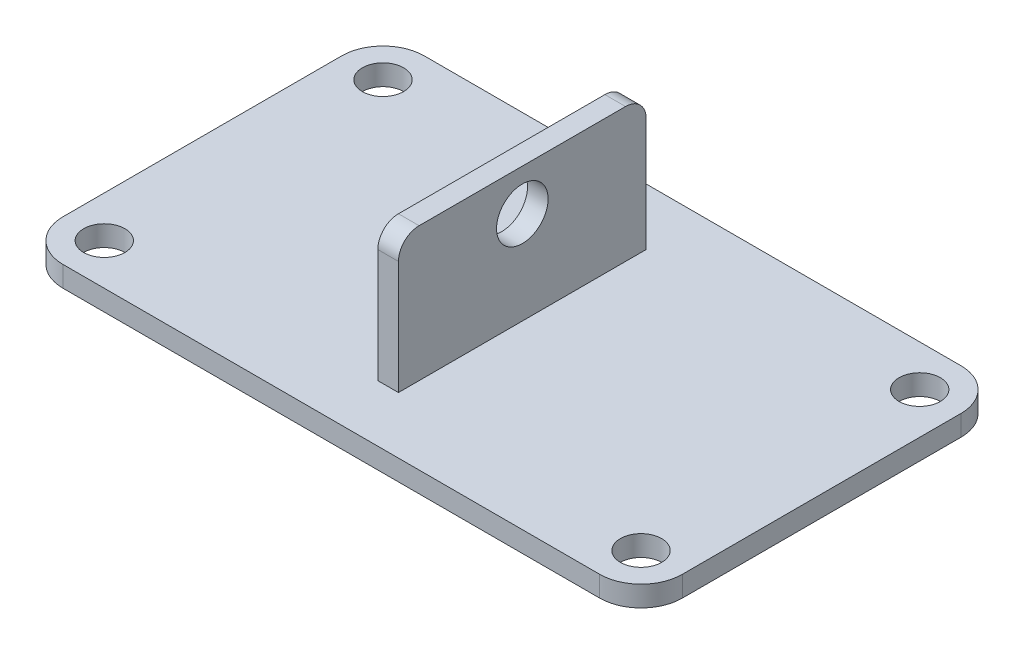
SolidWorks part; units mm, degrees
ref_plane "Front Plane" through (0, 0, 0) normal (0, 0, 1) x (1, 0, 0)
ref_plane "Top Plane" through (0, 0, 0) normal (0, 1, 0) x (1, 0, 0)
ref_plane "Right Plane" through (0, 0, 0) normal (1, 0, 0) x (0, 0, -1)
sketch "Sketch1" plane through (0, 0, 0) normal (0, 1, 0) x (1, 0, 0)
  line L1 (-130, -87.5) -> (130, -87.5)
  line L2 (-150, -67.5) -> (-150, 67.5)
  line L3 (-130, 87.5) -> (130, 87.5)
  line L4 (150, -67.5) -> (150, 67.5)
  line L5 (-150, -87.5) -> (150, 87.5) construction
  line L6 (-150, 87.5) -> (150, -87.5) construction
  line L7 (-5, -60) -> (5, -60)
  line L8 (-5, -60) -> (-5, 60)
  line L9 (-5, 60) -> (5, 60)
  line L10 (5, -60) -> (5, 60)
  line L11 (-5, -60) -> (5, 60)
  line L12 (-5, 60) -> (5, -60) construction
  arc A0 (-150, -67.5) -> (-130, -87.5) centre (-130, -67.5) ccw
  arc A1 (130, -87.5) -> (150, -67.5) centre (130, -67.5) ccw
  arc A2 (150, 67.5) -> (130, 87.5) centre (130, 67.5) ccw
  arc A3 (-150, 67.5) -> (-130, 87.5) centre (-130, 67.5) cw
  circle A4 centre (130, 67.5) radius 10
  circle A5 centre (130, -67.5) radius 10
  circle A6 centre (-130, 67.5) radius 10
  circle A7 centre (-130, -67.5) radius 10
  point P0 (0, 0)
  point P6 (0, 0)
  point P27 (0, 0)
  point P28 (0, 0)
  dimension "D3" = 20
  dimension "D4" = 10
  dimension "D6" = 20
  dimension "D1" = 175
  dimension "D2" = 300
  dimension "D5" = 120
extrude "Boss-Extrude1" add sketch "Sketch1" along normal blind 10 contours A3 L2 A0 L1 A1 L4 A2 L3 A7 A6 A5 A4 L10 L7 L8 L9 | L8 L11 L9 | L11 L7 L10 region at (-141.6863, 0, 79.1863) region at (1.6667, 0, 20) region at (-1.6667, 0, -20)
extrude "Boss-Extrude2" add sketch "Sketch1<3>" along normal blind 75 contours L8 L11 L9 | L8 L7 L10 L9 region at (-1.6667, 0, -20)
sketch "Sketch1<3>" plane through (0, 0, 0) normal (0, 1, 0) x (1, 0, 0) same geometry as "Sketch1"
sketch "Sketch2" plane through (5, 0, 0) normal (1, 0, 0) x (0, 0, -1)
  line L0 (0, 0) -> (0, 55)
  line L1 (-60, 65) -> (-60, 75)
  line L2 (-60, 10) -> (-60, 65)
  line L3 (-50, 75) -> (50, 75)
  line L4 (60, 65) -> (60, 10)
  line L5 (60, 10) -> (-60, 10)
  line L6 (-60, 75) -> (-50, 75)
  line L7 (-50, 75) -> (-60, 75)
  circle A0 centre (0, 55) radius 12.5
  arc A1 (-50, 75) -> (-60, 65) centre (-50, 65) ccw
  arc A2 (60, 65) -> (50, 75) centre (50, 65) ccw
  arc A3 (-50, 75) -> (-60, 65) centre (-50, 65) ccw
  point P14 (-60, 75)
  point P17 (60, 75)
  line M2 (60, 10) -> (60, 75)
  line M3 (60, 75) -> (-60, 75)
  line M4 (-60, 75) -> (-60, 10)
  dimension "D1" = 10
  dimension "D2" = 10
extrude "Cut-Extrude1" cut sketch "Sketch2" against normal blind 10 contours A0 | A1 M3 M4 | A2 M2 M3 region at (5, 63.5888, 8.5888) region at (5, 72.7663, -57.7663) region at (5, 72.7663, 57.7663)
